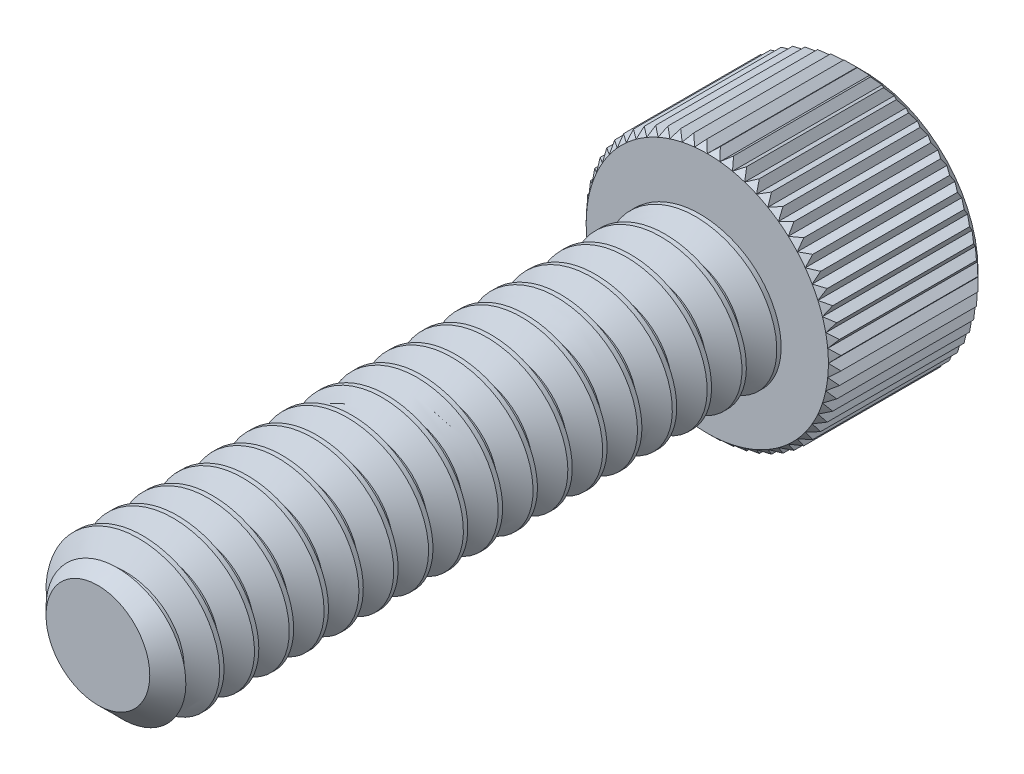
SolidWorks part; units mm, degrees
note: '?' marks a value the reader was unsure of.
ref_plane "Front Plane" through (0, 0, 0) normal (0, 0, 1) x (1, 0, 0)
ref_plane "Top Plane" through (0, 0, 0) normal (0, 1, 0) x (1, 0, 0)
ref_plane "Right Plane" through (0, 0, 0) normal (1, 0, 0) x (0, 0, -1)
sketch "Sketch0" plane through (0, 0, 0) normal (1, 0, 0) x (0, 0, -1)
  line L0 (0, 0) -> (11.1125, 0) construction
  point P2 (13.9573, 0)
  point P4 (0, 0)
  dimension "D1" = 11.1125
  dimension "D2" = 2.8448
  dimension "Min Thread" = 0
sketch "Sketch1" plane through (0, 0, 0) normal (0, 0, 1) x (1, 0, 0)
  circle A0 centre (0, 0) radius 1.4224
  dimension "OD" = 2.8448
extrude "Extrude1" add sketch "Sketch1" against normal blind 11.1125
sketch "Sketch2" plane through (0, 0, 0) normal (0, 0, 1) x (1, 0, 0)
  circle A0 centre (0, 0) radius 1.4224 construction
  circle A1 centre (0, 0) radius 1.4224
curve "Helix/Spiral1" pitch 0.635 height 11.7475 turns 18.5 parameters "pitch"=0.635
chamfer "Chamfer3" distance 0.4763 angle 45 1 edges at (1.4224, 0, 0)
sketch "Sketch3" plane through (0, 0, 0) normal (1, 0, 0) x (0, 0, -1)
  line L0 (-0.5556, 1.4224) -> (-0.3175, 1.01)
  line L1 (-0.3175, 1.01) -> (-0.2381, 1.01)
  line L2 (-0.2381, 1.01) -> (0, 1.4224)
  line L3 (-0.5556, 1.4224) -> (0, 1.4224)
  line L4 (-0.2778, 1.4224) -> (-0.2778, 1.01) construction
  line L5 (-0.4366, 1.2162) -> (-0.1191, 1.2162) construction
  line L6 (0, 1.4224) -> (0, -1.4224) construction
  dimension "D1" = 0.0794
  dimension "D2" = 0.3175
  dimension "D3" = 60
sweep "Cut-Sweep1" cut profiles "Sketch3" path "Helix/Spiral1" align with end faces yes
sketch "Sketch5" plane through (0, 0, 0) normal (1, 0, 0) x (0, 0, -1)
  line L0 (11.1125, -1.0149) -> (11.1125, 1.0232) construction
  line L1 (11.1125, 1.4224) -> (0, 1.4224)
  line L2 (11.1125, 1.4224) -> (11.1125, 0)
  line L3 (11.1125, 0) -> (-0.5177, 0)
  line L4 (0, 0) -> (11.1125, 0) construction
  line L5 (0, 1.4224) -> (-0.5177, 0)
  line L6 (0, 0) -> (13.6525, 0) construction
  dimension "D1" = 70
  dimension "D3" = 2.54
revolve "partially thread" [suppressed] add sketch "Sketch5" angle 360 about L6
sketch "Sketch6" plane through (0, 0, -11.1125) normal (0, 0, -1) x (-1, 0, 0)
  circle A0 centre (0, 0) radius 2.3241
  dimension "head dia" = 4.6482
extrude "Extrude2" add sketch "Sketch6" along normal blind 2.8448
sketch "Sketch7" plane through (0, 0, -13.9573) normal (0, 0, -1) x (-1, 0, 0)
  line L1 (0, 1.3748) -> (-1.1906, 0.6874)
  line L2 (-1.1906, 0.6874) -> (-1.1906, -0.6874)
  line L3 (-1.1906, -0.6874) -> (0, -1.3748)
  line L4 (0, -1.3748) -> (1.1906, -0.6874)
  line L5 (1.1906, -0.6874) -> (1.1906, 0.6874)
  line L6 (1.1906, 0.6874) -> (0, 1.3748)
  circle A0 centre (0, 0) radius 1.1906 construction
  dimension "hex dia" = 2.3813
extrude "Cut-Extrude1" cut sketch "Sketch7" against normal blind 1.7859
sketch "Sketch8" plane through (0, 0, -13.9573) normal (0, 0, -1) x (-1, 0, 0)
  circle A0 centre (0, 0) radius 1.3748
extrude "Cut-Extrude2" cut sketch "Sketch8" against normal through all draft 45
chamfer "Chamfer1" distance 0.2324 angle 45 1 edges at (-2.3241, 0, -13.9573)
chamfer "Chamfer2" distance 0.1162 angle 45 1 edges at (-2.3241, 0, -11.1125)
sketch "Sketch9" plane through (0, 0, 0) normal (1, 0, 0) x (0, 0, -1)
  line L0 (0, 1.4224) -> (0, -1.4224) construction
  line L1 (1.5875, 1.4224) -> (1.5875, -1.4224) construction
  line L2 (13.9573, 2.3241) -> (13.9573, -2.3241) construction
  line L3 (11.1125, 2.3241) -> (11.1125, -2.3241) construction
  line L4 (11.1125, 2.2079) -> (11.1125, -2.2079) construction
  line L5 (13.9573, -2.0917) -> (13.9573, 2.0917) construction
  line L6 (11.1125, -2.3241) -> (11.1125, 2.3241) construction
  line L7 (0, 0.9461) -> (0, -0.9461) construction
  line L8 (-0.5556, 1.4224) -> (0, 1.4224) construction
  line L9 (1.5875, 0) -> (0, 0) construction
  dimension "D1" = 1.5875
sketch "Sketch10" plane through (0, 0, -11.1125) normal (0, 0, 1) x (1, 0, 0)
  line L0 (-0.2501, 2.4403) -> (0, 2.2079)
  line L1 (0, 2.2079) -> (0.2501, 2.4403)
  line L2 (0, 2.2079) -> (0, 2.4403) construction
  line L3 (-0.2501, 2.4403) -> (0.2501, 2.4403)
  line L4 (0, -2.553) -> (0, 2.553) construction
  line L5 (0, 0) -> (0.1216, 2.3209) construction
  line L6 (-0.1216, 2.3209) -> (0, 0) construction
  circle A2 centre (0, 0) radius 2.3241 construction
  circle A5 centre (0, 0) radius 2.2079 construction
  dimension "D1" = 6
  dimension "D2" = 0.2324
extrude "Cut-Extrude3" cut sketch "Sketch10" against normal through all
pattern_circular "CirPattern1" count 60 over 360 about axis through (0, 0, 0) along (0, 0, 1) of "Cut-Extrude3"
ref_plane "Contact Plane 1" through (0, 0, -11.1125) normal (0, 0, 1) x (1, 0, 0)
ref_axis "Center Axis 1" through (0, 0, 0.8878) along (0, 0, -1)?
equation "\"D3@Helix/Spiral1\" = \"screw length@Extrude1\"+\"pitch@Helix/Spiral1\""
equation "\"D1@Sketch3\" = \"pitch@Helix/Spiral1\"*.125"
equation "\"D2@Sketch3\" = \"pitch@Helix/Spiral1\"*.5"
equation "\"D1@Cut-Extrude1\" = \"hex dia@Sketch7\"*.75"
equation "\"D1@Chamfer1\" = \"head dia@Sketch6\"*.05"
equation "\"D1@Sketch9\" = \"pitch@Helix/Spiral1\"*2.50"
equation "\"D1@Chamfer2\" = \"D1@Chamfer1\"/2"
equation "\"D1@Chamfer3\" = \"pitch@Helix/Spiral1\"*.750"
equation "\"D1@Sketch0\" = \"screw length@Extrude1\""
equation "\"D2@Sketch0\" = \"head depth@Extrude2\""
equation "\"D2@Sketch10\"=\"D1@Chamfer1\""
equation "\"D1@CirPattern1\"=\"D3@CirPattern1\"/\"D1@Sketch10\""
